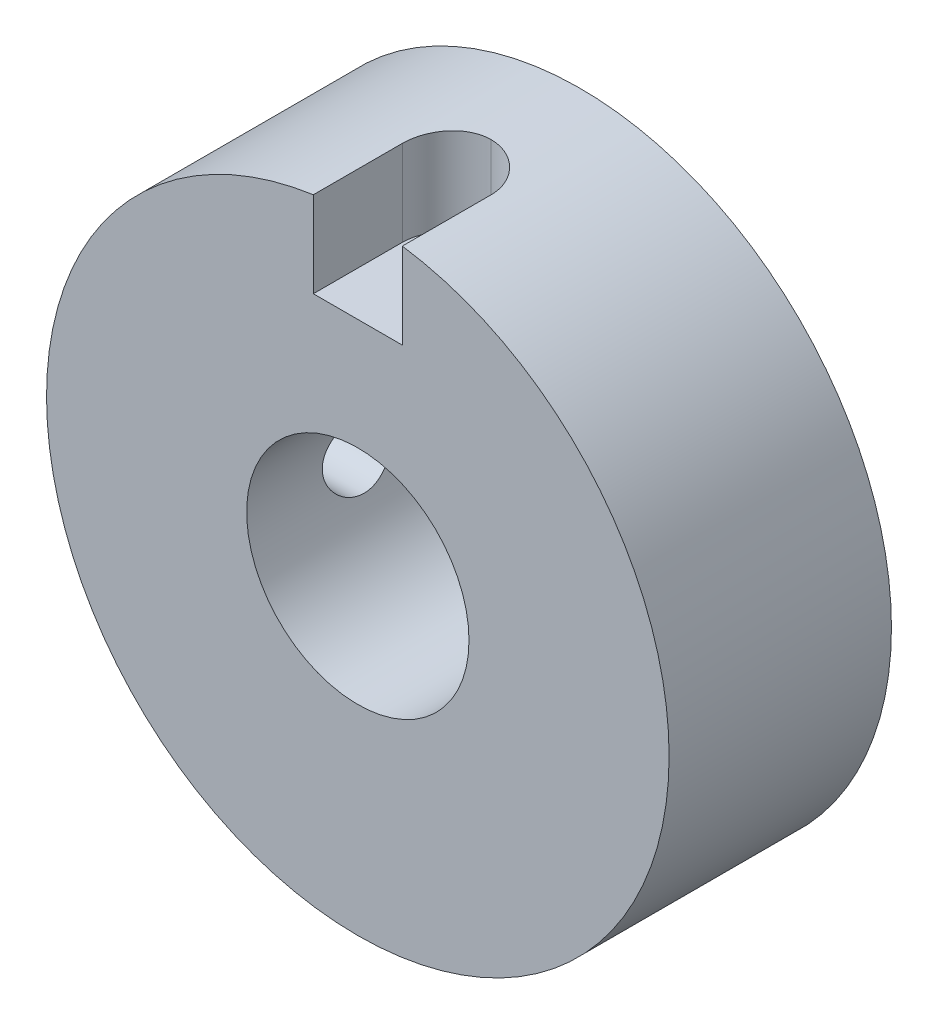
SolidWorks part; units mm, degrees
ref_plane "Front Plane" through (0, 0, 0) normal (0, 0, 1) x (1, 0, 0)
ref_plane "Top Plane" through (0, 0, 0) normal (0, 1, 0) x (1, 0, 0)
ref_plane "Right Plane" through (0, 0, 0) normal (1, 0, 0) x (0, 0, -1)
sketch "Sketch1" plane through (0, 0, 0) normal (0, 0, 1) x (1, 0, 0)
  circle A0 centre (0, 0) radius 35
  dimension "D1" = 70
extrude "Extrude1" add sketch "Sketch1" along normal blind 25
sketch "Sketch2" plane through (0, 0, 25) normal (0, 0, 1) x (1, 0, 0)
  circle A0 centre (0, 0) radius 12.5
  dimension "D1" = 25
extrude "Cut-Extrude1" cut sketch "Sketch2" against normal through all
sketch "Sketch3" plane through (0, 0, 25) normal (0, 0, 1) x (1, 0, 0)
  line L1 (-5, 40.7349) -> (5, 40.7349)
  line L2 (-5, 40.7349) -> (-5, 25)
  line L3 (-5, 25) -> (5, 25)
  line L4 (5, 40.7349) -> (5, 25)
  dimension "D1" = 10
  dimension "D2" = 5
  dimension "D3" = 25
extrude "Cut-Extrude2" cut sketch "Sketch3" against normal blind 15
fillet "Fillet1" radius 5 2 edges at (-5, 29.8205, 10) (5, 29.8205, 10)
sketch "Sketch4" plane through (0, 0, 0) normal (0, 0, -1) x (-1, 0, 0)
  circle A0 centre (0, 0) radius 22.5
  dimension "D1" = 45
extrude "Cut-Extrude4" cut sketch "Sketch4" against normal blind 5
sketch "Sketch5" plane through (0, 0, 0) normal (1, 0, 0) x (0, 0, -1)
  line L0 (0, 0) -> (-25, -0.1795) construction
  line L1 (0, -35) -> (0, 35) construction
  line L3 (-25, 34.641) -> (-25, -35) construction
  circle A0 centre (-12.5, -0.0897) radius 4
  point P6 (-12.5, -0.0897)
  point P11 (-25, -0.1795)
  dimension "D1" = 8
extrude "Side hole" cut sketch "Sketch5" against normal through all
